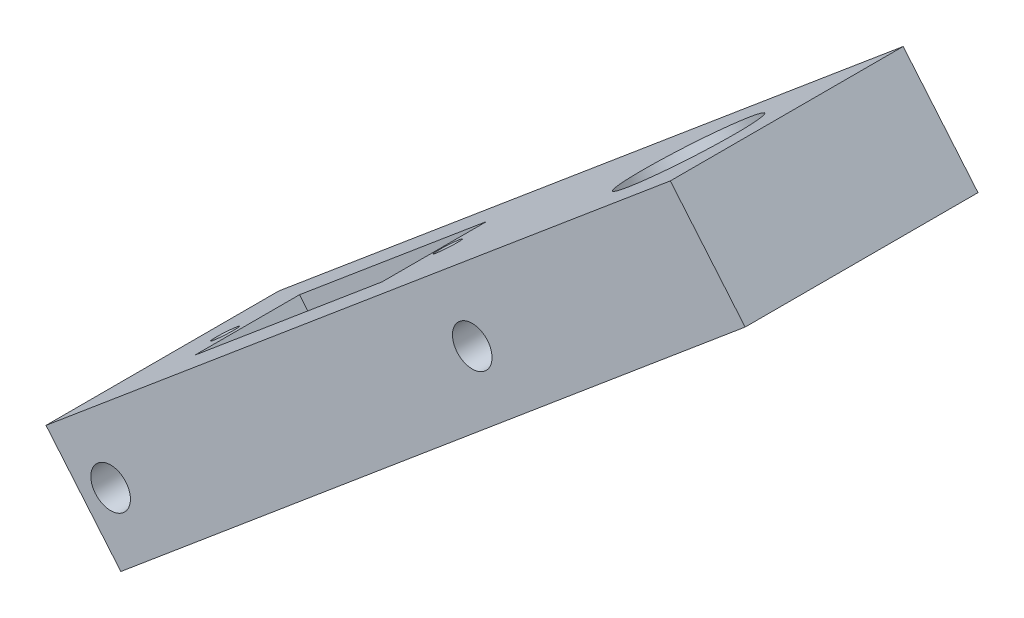
SolidWorks part; units mm, degrees
ref_plane "前视基准面" through (0, 0, 0) normal (0, 0, 1) x (1, 0, 0)
ref_plane "上视基准面" through (0, 0, 0) normal (0, 1, 0) x (1, 0, 0)
ref_plane "右视基准面" through (0, 0, 0) normal (1, 0, 0) x (0, 0, -1)
ref_axis "基准轴2" through (0, 0, -88.99) along (0, 0, 1)
ref_plane "基准面1" through (0, 0, 0) normal (-0.6428, 0.766, 0) x (0, 0, 1)
sketch "草图1" plane through (0, 0, 0) normal (-0.6428, 0.766, 0) x (0.766, 0.6428, 0)
  line L1 (10.5, 4.5) -> (-10.5, 4.5)
  line L2 (10.5, 4.5) -> (10.5, -4.5)
  line L3 (10.5, -4.5) -> (-10.5, -4.5)
  line L4 (-10.5, 4.5) -> (-10.5, -4.5)
  line L5 (10.5, 4.5) -> (-10.5, -4.5) construction
  line L6 (10.5, -4.5) -> (-10.5, 4.5) construction
  line L11 (-20, 10) -> (50, 10)
  line L12 (-20, 10) -> (-20, -10)
  line L13 (-20, -10) -> (50, -10)
  line L14 (50, 10) -> (50, -10)
  point P0 (0, 0)
  point P6 (0, 0)
extrude "凸台-拉伸1" add sketch "草图1" along normal blind 10
sketch "草图3" plane through (-6.4279, 7.6604, 0) normal (-0.6428, 0.766, 0) x (0.766, 0.6428, 0)
  circle A0 centre (39, 0) radius 5.2
  circle A1 centre (-13, 0) radius 1
  circle A2 centre (12, 0) radius 1
extrude "切除-拉伸1" cut sketch "草图3" against normal up to next
sketch "草图4" plane through (0, 0, 10) normal (0, 0, 1) x (1, 0, 0)
  line L0 (-18.5348, -9.0255) -> (35.0883, 35.9696) construction
  line L1 (-21.7488, -5.1953) -> (-15.3209, -12.8558) construction
  line L2 (31.8743, 39.7998) -> (38.3022, 32.1394) construction
  circle A0 centre (-16.1982, -7.0649) radius 1.7
  circle A1 centre (14.8626, 18.9983) radius 1.7
extrude "切除-拉伸2" cut sketch "草图4" against normal up to next
